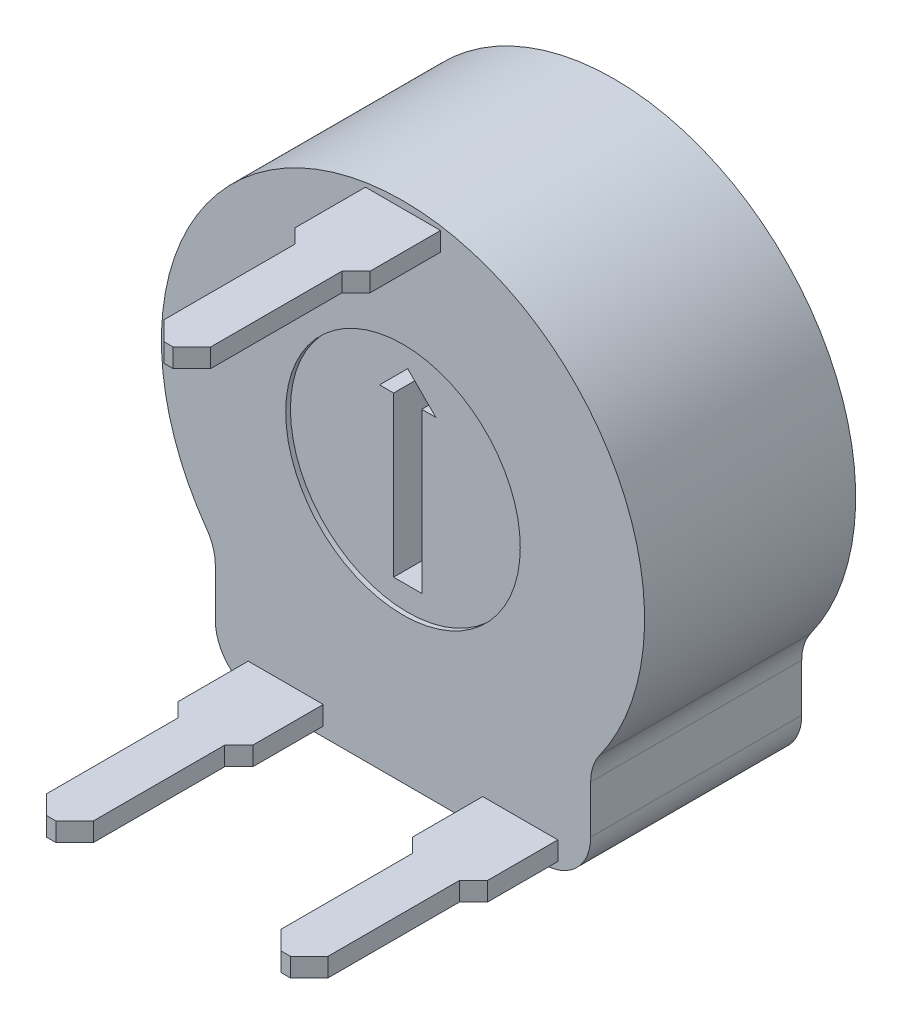
SolidWorks part; units mm, degrees
ref_plane "Plan de face" through (0, 0, 0) normal (0, 0, 1) x (1, 0, 0)
ref_plane "Plan de dessus" through (0, 0, 0) normal (0, 1, 0) x (1, 0, 0)
ref_plane "Plan de droite" through (0, 0, 0) normal (1, 0, 0) x (0, 0, -1)
sketch "Esquisse1" plane through (0, 0, 0) normal (0, 0, 1) x (1, 0, 0)
  line L0 (-4, -3.2438) -> (-4, -5.6)
  line L1 (-4, -5.6) -> (4, -5.6)
  line L2 (4, -5.6) -> (4, -3.2438)
  arc A0 (-4, -3.2438) -> (4, -3.2438) centre (0, 0) cw
  point P4 (0, 0)
  dimension "D1" = 5.15
  dimension "D2" = 5.6
  dimension "D3" = 8
extrude "Boss.-Extru.1" add sketch "Esquisse1" along normal blind 4.5
sketch "Esquisse4" plane through (0, 0, 0) normal (0, 0, -1) x (-1, 0, 0)
  circle A0 centre (0, 0) radius 2.5
  dimension "D1" = 5
extrude "Enlèv. mat.-Extru.1" cut sketch "Esquisse4" against normal blind 0.1
sketch "Esquisse5" plane through (0, 0, 4.5) normal (0, 0, 1) x (1, 0, 0)
  circle A0 centre (0, 0) radius 2.5
  dimension "D1" = 5
extrude "Enlèv. mat.-Extru.2" cut sketch "Esquisse5" against normal blind 0.1
sketch "Esquisse6" plane through (0, 0, 0.1) normal (0, 0, -1) x (-1, 0, 0)
  line L0 (0, 2) -> (-0.6, 1.4)
  line L1 (-0.6, 1.4) -> (-0.3, 1.4)
  line L2 (-0.3, 1.4) -> (-0.3, -2)
  line L3 (-0.3, -2) -> (0.3, -2)
  line L4 (0.3, -2) -> (0.3, 1.4)
  line L5 (0.3, 1.4) -> (0.6, 1.4)
  line L6 (0.6, 1.4) -> (0, 2)
  dimension "D1" = 0.3
  dimension "D2" = 0.3
  dimension "D3" = 45
  dimension "D4" = 2
  dimension "D5" = 2
  dimension "D6" = 1.2
extrude "Enlèv. mat.-Extru.3" cut sketch "Esquisse6" against normal through all
fillet "Congé1" radius 1 4 edges at (-4, -3.2438, 2.25) (-4, -5.6, 2.25) (4, -3.2438, 2.25) (4, -5.6, 2.25)
sketch "Esquisse7" plane through (0, 0, 4.5) normal (0, 0, 1) x (1, 0, 0)
  line L0 (-2.5, -5.2) -> (0, -5.2) construction
  line L1 (-3.3, -5.4) -> (-1.7, -5.4)
  line L2 (-3.3, -5.4) -> (-3.3, -5)
  line L3 (-3.3, -5) -> (-1.7, -5)
  line L4 (-1.7, -5.4) -> (-1.7, -5)
  line L5 (-3.3, -5.4) -> (-1.7, -5) construction
  line L6 (-3.3, -5) -> (-1.7, -5.4) construction
  line L7 (1.7, -5.4) -> (3.3, -5.4)
  line L8 (1.7, -5.4) -> (1.7, -5)
  line L9 (1.7, -5) -> (3.3, -5)
  line L10 (3.3, -5.4) -> (3.3, -5)
  line L11 (1.7, -5.4) -> (3.3, -5) construction
  line L12 (1.7, -5) -> (3.3, -5.4) construction
  line L13 (-0.8, 5) -> (0.8, 5)
  line L14 (-0.8, 5) -> (-0.8, 4.6)
  line L15 (-0.8, 4.6) -> (0.8, 4.6)
  line L16 (0.8, 5) -> (0.8, 4.6)
  line L17 (-0.8, 5) -> (0.8, 4.6) construction
  line L18 (-0.8, 4.6) -> (0.8, 5) construction
  line L19 (0, -5.2) -> (2.5, -5.2) construction
  line L20 (0, -5.2) -> (0, 4.8) construction
  line L21 (-3, -5.6) -> (3, -5.6) construction
  point P0 (-2.5, -5.2)
  point P5 (2.5, -5.2)
  point P10 (0, 4.8)
  dimension "D1" = 1.6
  dimension "D2" = 0.4
  dimension "D3" = 5
  dimension "D4" = 10
  dimension "D5" = 0.2
extrude "Boss.-Extru.4" add sketch "Esquisse7" along normal blind 1.5
sketch "Esquisse8" plane through (0, 0, 6) normal (0, 0, 1) x (1, 0, 0)
  line L0 (0.8, 5) -> (-0.8, 5) construction
  line L1 (-0.5, 5) -> (0.5, 5)
  line L2 (-0.5, 5) -> (-0.5, 4.6)
  line L3 (-0.5, 4.6) -> (0.5, 4.6)
  line L4 (0.5, 5) -> (0.5, 4.6)
  line L5 (-0.8, 4.6) -> (0.8, 4.6) construction
  line L6 (-1.7, -5) -> (-3.3, -5) construction
  line L7 (-3, -5) -> (-2, -5)
  line L8 (-3, -5) -> (-3, -5.4)
  line L9 (-3, -5.4) -> (-2, -5.4)
  line L10 (-2, -5) -> (-2, -5.4)
  line L11 (-3.3, -5.4) -> (-1.7, -5.4) construction
  line L12 (3.3, -5) -> (1.7, -5) construction
  line L13 (2, -5) -> (3, -5)
  line L14 (2, -5) -> (2, -5.4)
  line L15 (2, -5.4) -> (3, -5.4)
  line L16 (3, -5) -> (3, -5.4)
  line L17 (1.7, -5.4) -> (3.3, -5.4) construction
  line L18 (-0.8, 5) -> (-0.8, 4.6) construction
  line L19 (-3.3, -5) -> (-3.3, -5.4) construction
  line L20 (1.7, -5) -> (1.7, -5.4) construction
  dimension "D1" = 0.3
  dimension "D2" = 0.3
  dimension "D3" = 0.3
  dimension "D4" = 1
extrude "Boss.-Extru.5" add sketch "Esquisse8" along normal blind 3.5
chamfer "Chanfrein3" distance 0.3 angle 45 6 edges at (0.5, 4.8, 6) (-2, -5.2, 6) (3, -5.2, 6) (2, -5.2, 6) (-3, -5.2, 6) (-0.5, 4.8, 6)
chamfer "Chanfrein4" distance 0.4 angle 45 6 edges at (0.5, 4.8, 9.5) (-0.5, 4.8, 9.5) (3, -5.2, 9.5) (2, -5.2, 9.5) (-3, -5.2, 9.5) (-2, -5.2, 9.5)
